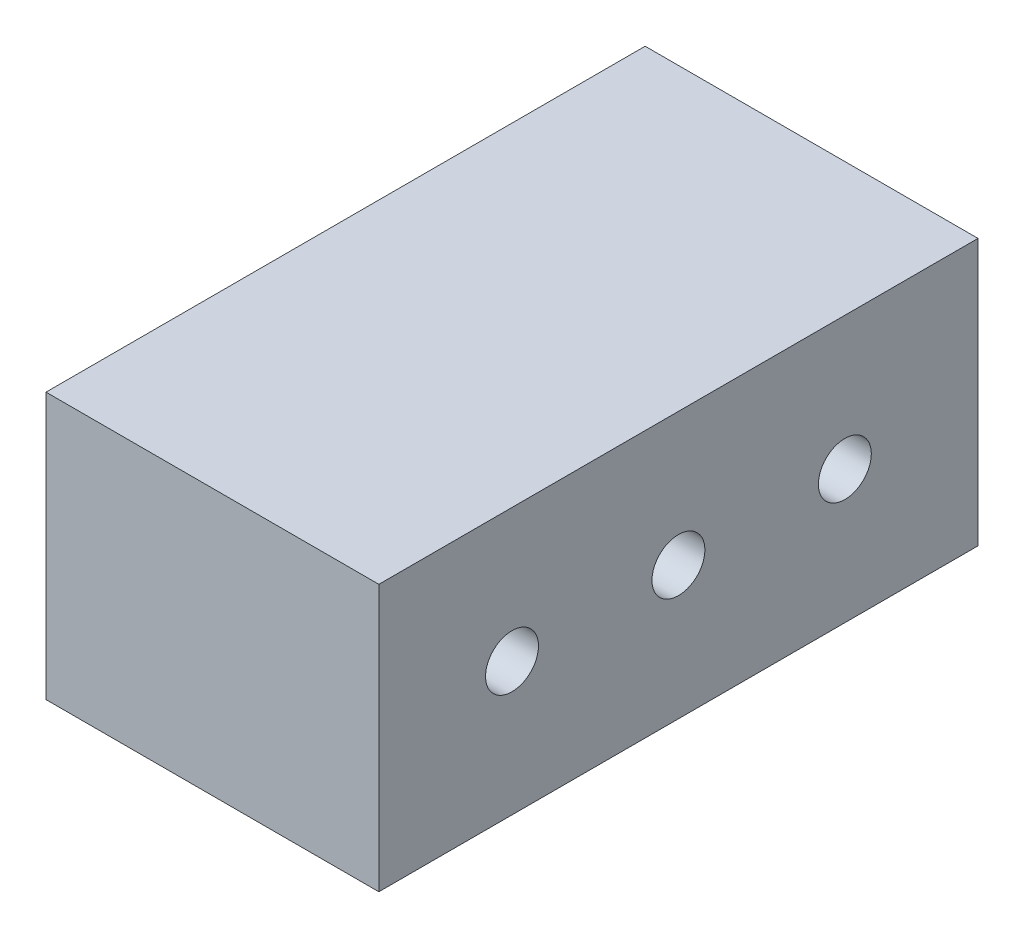
SolidWorks part; units mm, degrees
ref_plane "Front" through (0, 0, 0) normal (0, 0, 1) x (1, 0, 0)
ref_plane "Top" through (0, 0, 0) normal (0, 1, 0) x (1, 0, 0)
ref_plane "Right" through (0, 0, 0) normal (1, 0, 0) x (0, 0, -1)
sketch "Sketch1" plane through (0, 0, 0) normal (0, 1, 0) x (1, 0, 0)
  line L1 (-12.7, -22.86) -> (12.7, -22.86)
  line L2 (-12.7, -22.86) -> (-12.7, 22.86)
  line L3 (-12.7, 22.86) -> (12.7, 22.86)
  line L4 (12.7, -22.86) -> (12.7, 22.86)
  line L5 (-12.7, -22.86) -> (12.7, 22.86) construction
  line L6 (-12.7, 22.86) -> (12.7, -22.86) construction
  point P0 (0, 0)
  dimension "D1" = 25.4
  dimension "D2" = 45.72
extrude "Boss-Extrude1" add sketch "Sketch1" along normal blind 20.32
sketch "Sketch4" plane through (12.7, 0, 0) normal (1, 0, 0) x (0, 0, -1)
  line L1 (12.7, 10.16) -> (-12.7, 10.16) construction
  line L3 (-12.7, 0) -> (-12.7, 10.16) construction
  line L4 (-22.86, 0) -> (22.86, 0) construction
  line L5 (-12.7, 10.16) -> (-12.7, 20.32) construction
  line L6 (-22.86, 20.32) -> (22.86, 20.32) construction
  point P0 (-12.7, 10.16)
  point P2 (0, 10.16)
  point P4 (12.7, 10.16)
  point P66 (0, 10.16)
  point P82 (-12.7, 9.1522)
  dimension "D1" = 12.7
hole_wizard "#10-32 Tapped Hole1" positions "Sketch4" profile "Sketch3" tap size "#10-32" standard "ANSI Inch" end condition through all
cosmetic thread "Hole Thread1" parameters "D2"=4.826
cosmetic thread "Hole Thread2" parameters "D2"=4.826
cosmetic thread "Hole Thread3" parameters "D2"=4.826
sketch "Sketch3" plane through (12.7, 10.16, 12.7) normal (0, 1, 0) x (0, 0, -1)
  line L0 (0, 0) -> (0, 25.4)
  line L1 (0, 25.4) -> (2.0193, 25.4)
  line L2 (2.0193, 25.4) -> (2.0193, 0)
  line L5 (2.0193, 0) -> (0, 0)
  line L11 (0, -6.35) -> (0, 107.95) construction
  dimension "Thru Tap Drill Dia." = 4.0386
  dimension "Thru Tap Drill Depth" = 25.4
cosmetic thread "Hole Thread4" parameters "D2"=4.826
